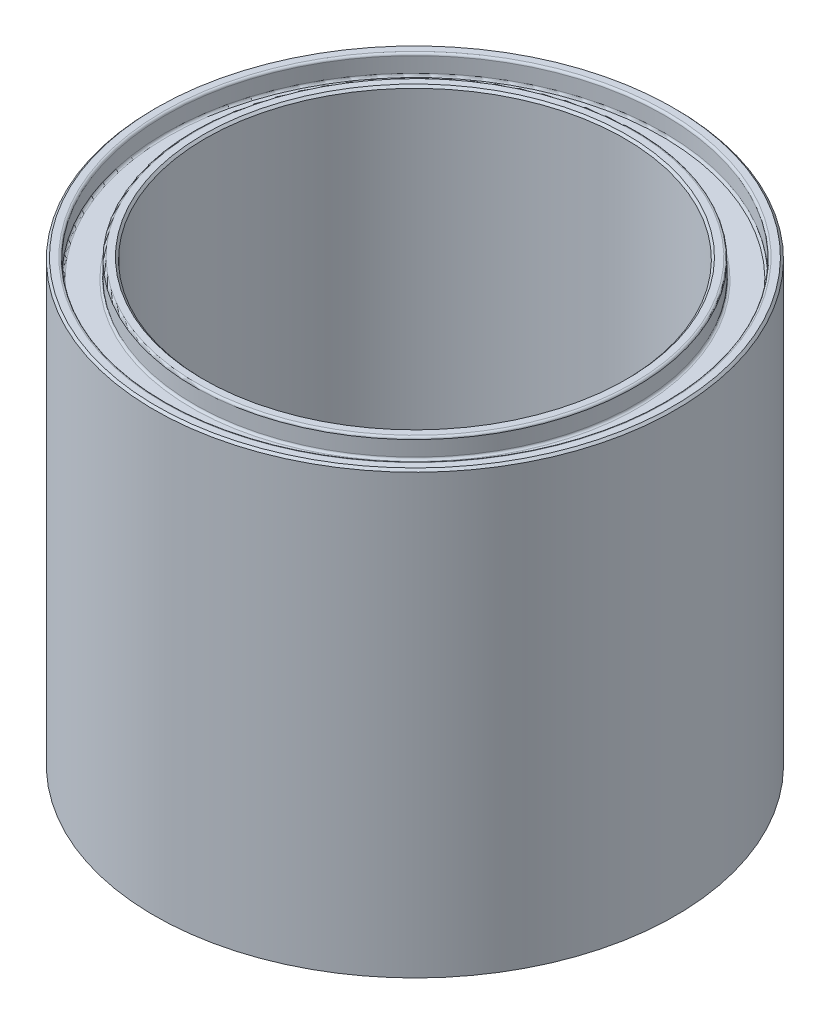
SolidWorks part; units mm, degrees
ref_plane "Front Plane" through (0, 0, 0) normal (0, 0, 1) x (1, 0, 0)
ref_plane "Top Plane" through (0, 0, 0) normal (0, 1, 0) x (1, 0, 0)
ref_plane "Right Plane" through (0, 0, 0) normal (1, 0, 0) x (0, 0, -1)
sketch "Sketch1" plane through (0, 0, 0) normal (0, 0, 1) x (1, 0, 0)
  line L0 (0, 0) -> (-47.3705, 0)
  line L1 (-47.3705, 0) -> (-47.3705, 80)
  line L3 (-38.1, 80) -> (-38.1, 15.5)
  line L4 (-28.1, 5.5) -> (0, 5.5)
  line L5 (0, 5.5) -> (0, 0)
  line L12 (-47.3705, 80) -> (-45.3705, 80)
  line L13 (-45.3705, 80) -> (-45.3705, 76.444)
  line L14 (-45.3705, 76.444) -> (-40.1, 76.444)
  line L15 (-40.1, 76.444) -> (-40.1, 80)
  line L16 (-40.1, 80) -> (-38.1, 80)
  arc A0 (-38.1, 15.5) -> (-28.1, 5.5) centre (-28.1, 15.5) ccw
  point P9 (-38.1, 5.5)
  dimension "D3" = 10
  dimension "D1" = 38.1
  dimension "D2" = 80
  dimension "D5" = 5.5
  dimension "D6" = 90
  dimension "D7" = 90
  dimension "D8" = 5.2705
  dimension "D4" = 2
  dimension "D9" = 3.556
revolve "Revolve1" add sketch "Sketch1" angle 360 about L5
sketch "Sketch2" [suppressed] plane through (0, 0, 0) normal (0, -1, 0) x (1, 0, 0)
  circle A0 centre (0, 0) radius 12.7 construction
  circle A1 centre (0, 12.7) radius 2.032
  point P3 (0, 12.7)
  point P7 (8.9803, 8.9803)
  point P8 (12.7, 0)
  point P9 (8.9803, -8.9803)
  point P10 (0, -12.7)
  point P11 (-8.9803, -8.9803)
  point P12 (-12.7, 0)
  point P13 (-8.9803, 8.9803)
  point P14 (0, 0)
  dimension "D1" = 25.4
  dimension "D3" = 4.064
  dimension "D2" = 8
extrude "Cut-Extrude1" [suppressed] cut sketch "Sketch2" against normal up to next draft 4.35 contours A1
pattern_circular "CirPattern1" [suppressed] count 4 over 360 of bodies 102
fillet "Fillet1" radius 0.3969 4 edges at (-40.1, 76.444, 0) (-45.3705, 80, 0) (-45.3705, 76.444, 0) (-40.1, 80, 0)
chamfer "Chamfer1" distance 0.3969 angle 45 2 edges at (-38.1, 80, 0) (-47.3705, 80, 0)
equation "\"groovedepth\" = 0.14"
equation "\"D9@Sketch1\"=\"groovedepth\""
